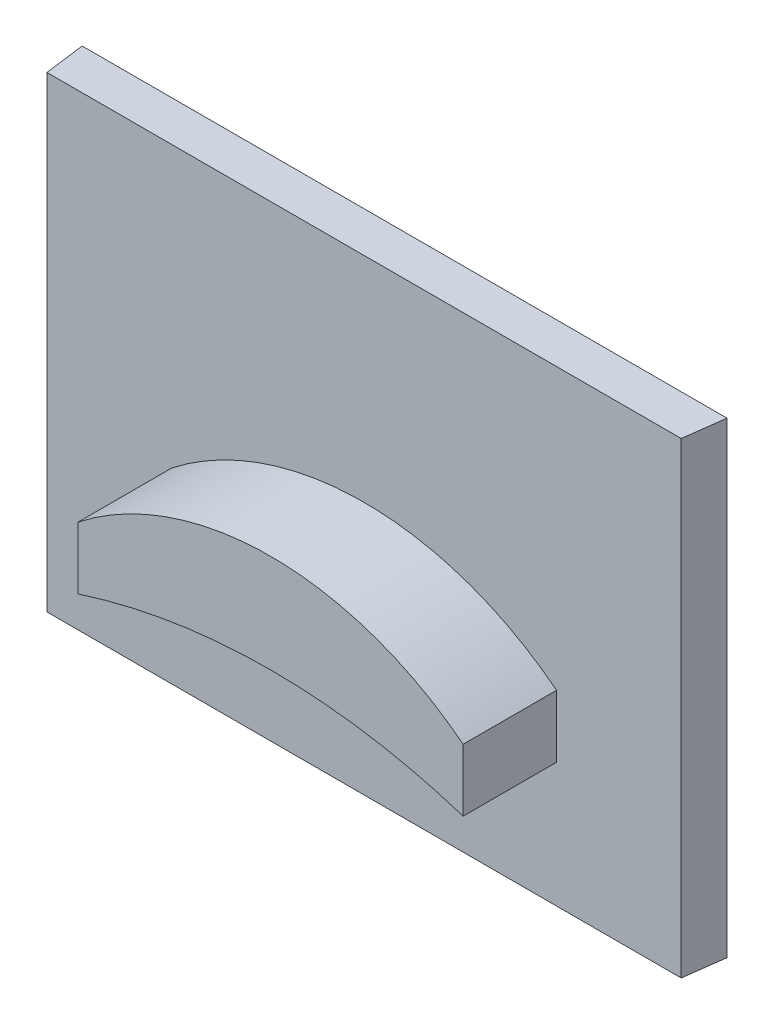
SolidWorks part; units mm, degrees
ref_plane "Plano frontal" through (0, 0, 0) normal (0, 0, 1) x (1, 0, 0)
ref_plane "Plano superior" through (0, 0, 0) normal (0, 1, 0) x (1, 0, 0)
ref_plane "Plano direito" through (0, 0, 0) normal (1, 0, 0) x (0, 0, -1)
sketch "Esboço1" plane through (0, 0, 0) normal (0, 1, 0) x (1, 0, 0)
  line L34 (10.1627, 85.0999) -> (10.3338, 86.3999)
  line L35 (-10.1945, 85.0959) -> (10.1627, 85.0999)
  line L36 (-10.3656, 86.3959) -> (10.3338, 86.3999)
  line L37 (-10.1947, 86.3959) -> (10.1624, 86.3999) construction
  line L38 (-10.3656, 86.3959) -> (-10.1945, 85.0959)
  point P41 (-10.4026, 86.6772)
  point P44 (10.3704, 86.6772)
  dimension "D1" = 20.6994
  dimension "D2" = 20.3571
  dimension "D3" = 1.3
extrude "Ressalto-extrusão1" add sketch "Esboço1" along normal blind 15
sketch "Esboço2" plane through (-0.0167, 0, -85.0979) normal (0.0002, 0, 1) x (1, 0, -0.0002)
  line L0 (-6.1778, 6) -> (-6.1778, 4)
  line L1 (6.1794, 4) -> (6.1794, 6)
  line L4 (-10.1778, 0) -> (10.1794, 0)
  line L5 (10.1794, 0) -> (10.1794, 15)
  line L6 (10.1794, 15) -> (-10.1778, 15)
  line L7 (-10.1778, 15) -> (-10.1778, 0)
  line L8 (-10.1778, 0) -> (10.1794, 0)
  line L9 (10.1794, 0) -> (10.1794, 15)
  line L10 (10.1794, 15) -> (-10.1778, 15)
  line L11 (-10.1778, 15) -> (-10.1778, 0)
  line L13 (-6.1778, 15) -> (-6.1778, 0) construction
  line L16 (6.1794, 0) -> (6.1794, 15) construction
  arc A0 (-6.1778, 4) -> (6.1794, 4) centre (0.0008, -15.0217) cw
  arc A1 (-6.1778, 6) -> (6.1794, 6) centre (0.0008, -1.8629) cw
  point P8 (10.1794, 6)
  point P9 (-10.1778, 6)
  point P10 (-10.1778, 4)
  point P11 (10.1794, 4)
  dimension "D5" = 20
  dimension "D9" = 10
  dimension "D6" = 4
  dimension "D7" = 4
  dimension "D4" = 6
  dimension "D11" = 6
  dimension "D1" = 0
  dimension "D2" = 4
  dimension "D3" = 4
extrude "Ressalto-extrusão2" add sketch "Esboço2" along normal blind 3 contours L0 A0 L1 A1
